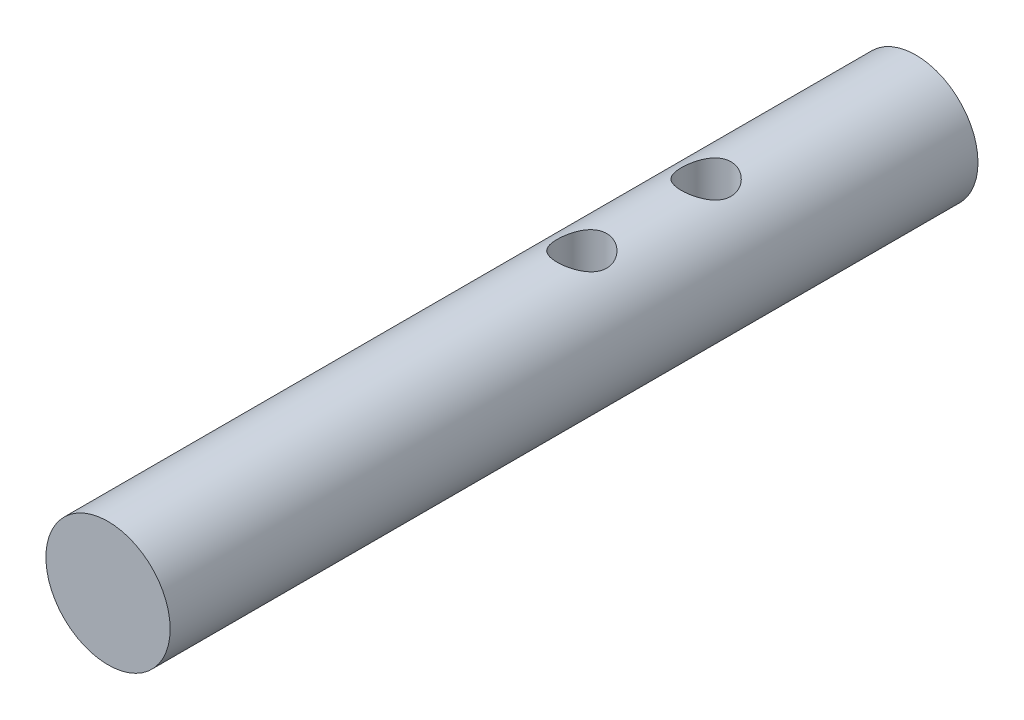
SolidWorks part; units mm, degrees
material "6061 合金"
ref_plane "正面" through (0, 0, 0) normal (0, 0, 1) x (1, 0, 0)
ref_plane "平面" through (0, 0, 0) normal (0, 1, 0) x (1, 0, 0)
ref_plane "右側面" through (0, 0, 0) normal (1, 0, 0) x (0, 0, -1)
sketch "断面" plane through (0, 0, 0) normal (0, 0, 1) x (1, 0, 0)
  circle A0 centre (0, 0) radius 4
  dimension "D1" = 8
extrude "軸全長" add sketch "断面" along normal blind 52
ref_axis "中心軸" through (0, 0, 52) along (0, 0, -1)
ref_plane "上面" through (0, 4, 0) normal (0, 1, 0) x (1, 0, 0)
sketch "上面穴スケッチ" plane through (0, 4, 0) normal (0, 1, 0) x (1, 0, 0)
  line L0 (0, -52) -> (0, 0) construction
  line L1 (4, 0) -> (-4, 0) construction
  circle A0 centre (0, -13.5) radius 1.6
  circle A1 centre (0, -21.5) radius 1.6
  dimension "D1" = 13.5
  dimension "D2" = 3.2
  dimension "D3" = 8
extrude "上面穴貫通" cut sketch "上面穴スケッチ" against normal through all
sketch "上面キー溝スケッチ" plane through (0, 4, 0) normal (0, 1, 0) x (1, 0, 0)
  line L0 (0, -30) -> (0, -50) construction
  line L1 (0, -52) -> (0, 0) construction
  line L2 (1.5, -30) -> (1.5, -50)
  line L3 (-1.5, -30) -> (-1.5, -50)
  line L4 (4, 0) -> (-4, 0) construction
  arc A0 (1.5, -30) -> (-1.5, -30) centre (0, -30) ccw
  arc A1 (-1.5, -50) -> (1.5, -50) centre (0, -50) ccw
  point P5 (0, -40)
  dimension "D1" = 3
  dimension "D2" = 30
  dimension "D3" = 20
extrude "上面キー溝1.6mm" [suppressed] cut sketch "上面キー溝スケッチ" against normal blind 1.6
sketch "上面Dカットスケッチ" plane through (0, 4, 0) normal (0, 1, 0) x (1, 0, 0)
  line L0 (-4, 0) -> (-4, -52) construction
  line L1 (4, -52) -> (-4, -52)
  line L2 (4, -52) -> (4, -42)
  line L3 (4, -42) -> (-4, -42)
  line L4 (-4, -52) -> (-4, -42)
  dimension "D1" = 10
extrude "上面Dカット1mm" [suppressed] cut sketch "上面Dカットスケッチ" against normal blind 1
sketch "Eリング溝スケッチ" plane through (0, 0, 0) normal (0, 1, 0) x (1, 0, 0)
  line L0 (4, -52) -> (4, 0) construction
  line L1 (4, -1) -> (3, -1)
  line L2 (4, -1) -> (4, -2)
  line L3 (4, -2) -> (3, -2)
  line L4 (3, -1) -> (3, -2)
  line L5 (4, 0) -> (-4, 0) construction
  dimension "D1" = 1
  dimension "D2" = 1
revolve "Eリング溝カット" [suppressed] cut sketch "Eリング溝スケッチ" angle 360 about axis through (0, 0, 52) along (0, 0, -1)
